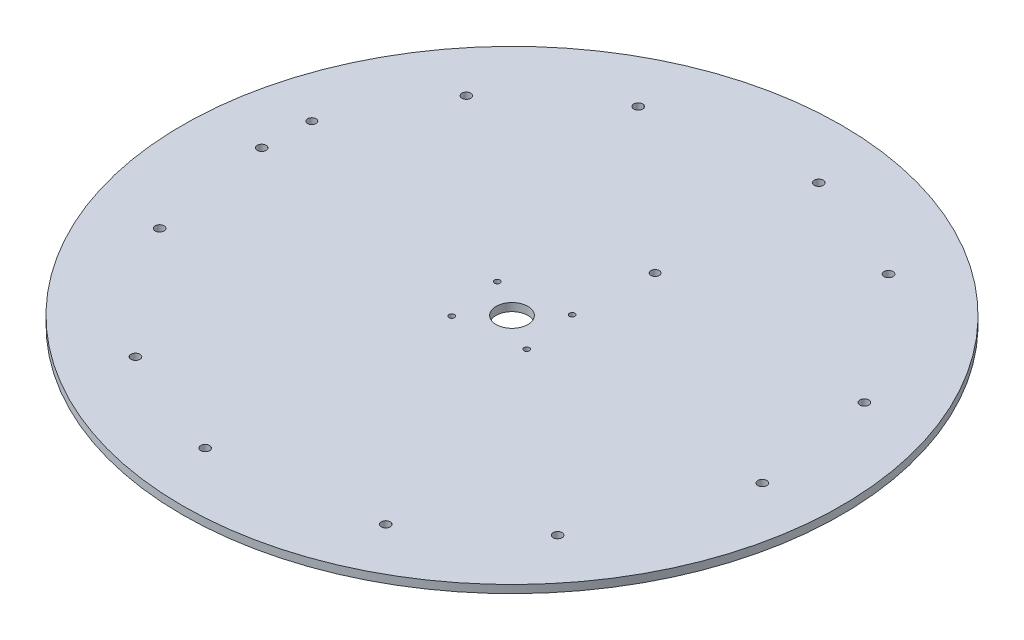
SolidWorks part; units mm, degrees
ref_plane "Front Plane" through (0, 0, 0) normal (0, 0, 1) x (1, 0, 0)
ref_plane "Top Plane" through (0, 0, 0) normal (0, 1, 0) x (1, 0, 0)
ref_plane "Right Plane" through (0, 0, 0) normal (1, 0, 0) x (0, 0, -1)
sketch "Sketch2" plane through (0, 0, 0) normal (0, 1, 0) x (1, 0, 0)
  circle A0 centre (0, 0) radius 125
  dimension "D1" = 250
extrude "Boss-Extrude1" add sketch "Sketch2" along normal blind 3
sketch "Sketch3" plane through (0, 3, 0) normal (0, 1, 0) x (1, 0, 0)
  line L4 (74.6446, 100.2656) -> (65.4599, 76.5843) construction
  line L5 (0, 0) -> (43.5629, 112.3204) construction
  line L6 (74.6446, 100.2656) -> (12.4813, 124.3753) construction
  line L7 (12.4813, 124.3753) -> (3.2966, 100.6941) construction
  line L8 (65.4599, 76.5843) -> (3.2966, 100.6941) construction
  circle A0 centre (0, 0) radius 125 construction
  circle A7 centre (57.8244, 84.9944) radius 1.7
  circle A8 centre (14.6061, 101.7564) radius 1.7
  circle A9 centre (44.6952, -92.5746) radius 1.7
  circle A10 centre (80.8206, -63.5274) radius 1.7
  circle A11 centre (-102.5195, 7.5802) radius 1.7
  circle A12 centre (-95.4267, -38.229) radius 1.7
  point P22 (0, 0)
  point P23 (0.4661, 0.2121)
  dimension "D2" = 3.4
  dimension "D1" = 25.4
  dimension "D3" = 5.08
  dimension "D5" = 66.675
  dimension "D6" = 3
  dimension "D4" = 10.16
extrude "Cut-Extrude1" cut sketch "Sketch3" against normal blind 26 and the other way blind 62
sketch "Sketch4" plane through (0, 3, 0) normal (0, 1, 0) x (1, 0, 0)
  circle A0 centre (0, 0) radius 6
  dimension "D1" = 12
extrude "Cut-Extrude2" cut sketch "Sketch4" against normal blind 33 and the other way blind 55
sketch "Sketch5" plane through (0, 0, 0) normal (0, -1, 0) x (1, 0, 0)
  circle A0 centre (-101.7781, -25.8548) radius 1.6
  circle A1 centre (13.2168, -41.0922) radius 1.6
  dimension "D1" = 3.2
  dimension "D2" = 3.2
extrude "Cut-Extrude3" cut sketch "Sketch5" against normal through all
sketch "Sketch6" plane through (0, 3, 0) normal (0, 1, 0) x (1, 0, 0)
  circle A0 centre (11.1984, 11.6251) radius 1.05
  circle A1 centre (13.8892, -8.3009) radius 1.05
  circle A2 centre (-11.1984, -11.6251) radius 1.05
  circle A3 centre (-13.8892, 8.3009) radius 1.05
extrude "Cut-Extrude4" cut sketch "Sketch6" against normal up to next
pattern_circular "CirPattern1" count 6 over 360 about axis through (0, 3, 0) along (0, 1, 0) of "Cut-Extrude1"
